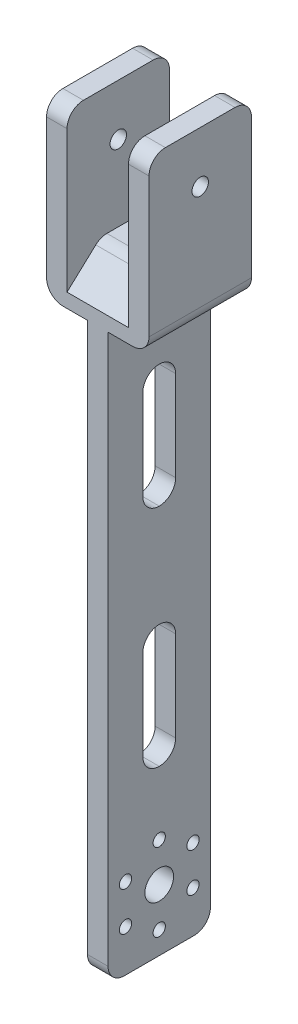
SolidWorks part; units mm, degrees
ref_plane "Ön Düzlem" through (0, 0, 0) normal (0, 0, 1) x (1, 0, 0)
ref_plane "Üst Düzlem" through (0, 0, 0) normal (0, 1, 0) x (1, 0, 0)
ref_plane "Sağ Düzlem" through (0, 0, 0) normal (1, 0, 0) x (0, 0, -1)
sketch "Çizim1" plane through (0, 0, 0) normal (0, 0, 1) x (1, 0, 0)
  line L0 (-2.5, 69) -> (-12.5, 69)
  line L1 (2.5, -69) -> (-2.5, -69)
  line L2 (2.5, -69) -> (2.5, 69)
  line L4 (-2.5, -69) -> (-2.5, 69)
  line L5 (2.5, -69) -> (-2.5, 69) construction
  line L6 (2.5, 69) -> (-2.5, -69) construction
  line L7 (-12.5, 69) -> (-12.5, 111)
  line L8 (-12.5, 111) -> (-7.5, 111)
  line L9 (-7.5, 111) -> (-7.5, 80)
  line L10 (-7.5, 80) -> (7.5, 80)
  line L11 (7.5, 80) -> (7.5, 111)
  line L12 (7.5, 111) -> (12.5, 111)
  line L13 (12.5, 111) -> (12.5, 69)
  line L14 (12.5, 69) -> (2.5, 69)
  point P0 (0, 0)
  dimension "D1" = 138
  dimension "D2" = 5
  dimension "D3" = 10
  dimension "D4" = 42
  dimension "D5" = 5
  dimension "D6" = 31
  dimension "D7" = 15
  dimension "D8" = 42
  dimension "D9" = 5
  dimension "D10" = 138
extrude "Yükseklik-Ekstrüzyon1" add sketch "Çizim1" along normal blind 25
sketch "Çizim2" plane through (-12.5, 0, 0) normal (-1, 0, 0) x (0, 0, 1)
  line L0 (0, 111) -> (0, 69) construction
  line L2 (25, 111) -> (0, 111) construction
  circle A0 centre (12.5, 98.5) radius 2
  dimension "D3" = 4
  dimension "D1" = 12.5
  dimension "D2" = 12.5
extrude "Kes-Ekstrüzyon1" cut sketch "Çizim2" against normal blind 25
sketch "Çizim3" plane through (-2.5, 0, 0) normal (-1, 0, 0) x (0, 0, 1)
  line L0 (25, 69) -> (25, -69) construction
  line L1 (8.5, 56) -> (16.5, 56)
  line L2 (8.5, 56) -> (8.5, 26)
  line L3 (8.5, 26) -> (16.5, 26)
  line L4 (16.5, 56) -> (16.5, 26)
  line L5 (8.5, 1) -> (16.5, 1)
  line L6 (8.5, 1) -> (8.5, -29)
  line L7 (8.5, -29) -> (16.5, -29)
  line L8 (16.5, 1) -> (16.5, -29)
  line L9 (25, -69) -> (0, -69) construction
  line L10 (0, 69) -> (0, -69) construction
  circle A0 centre (12.5, -54) radius 3.5
  dimension "D1" = 7
  dimension "D2" = 12.5
  dimension "D3" = 15
  dimension "D4" = 8.5
  dimension "D5" = 8.5
  dimension "D6" = 25
  dimension "D7" = 40
  dimension "D8" = 30
  dimension "D9" = 30
  dimension "D10" = 8.5
  dimension "D11" = 8.5
extrude "Kes-Ekstrüzyon2" cut sketch "Çizim3" against normal blind 10
sketch "Çizim4" plane through (-2.5, 0, 0) normal (-1, 0, 0) x (0, 0, 1)
  line L0 (25, 69) -> (25, -69) construction
  circle A0 centre (12.5, -44.5) radius 1.5
  dimension "D3" = 3
  dimension "D1" = 12.5
  dimension "D2" = 9.5
extrude "Kes-Ekstrüzyon3" cut sketch "Çizim4" against normal blind 10
pattern_circular "Dairesel Kaplama2" count 6 over 360 about axis through (7.5, -54, 12.5) along (-1, 0, 0) of "Kes-Ekstrüzyon3"
ref_plane "Plane1" through (0, 0, 0) normal (1, 0, 0) x (0, 0, -1)
sketch "Sketch2" plane through (0, 0, 0) normal (1, 0, 0) x (0, 0, -1)
  line L0 (-12.5, 0) -> (-12.5, 84) construction
  line L4 (0, 0) -> (-27.6764, 0) construction
  line L6 (-12.5, 84) -> (-25.5, 72)
  line L8 (-12.5, 84) -> (0.5, 72)
  line L9 (0.5, 72) -> (0.5, 86)
  line L10 (-25.5, 72) -> (-25.5, 86)
  line L11 (0.5, 86) -> (-25.5, 86)
  point P3 (0, 0)
  dimension "D1" = 12.5
  dimension "D2" = 84
  dimension "D3" = 13
  dimension "D4" = 13
  dimension "D5" = 12
  dimension "D6" = 12
  dimension "D7" = 14
  dimension "D8" = 14
extrude "Cut-Extrude8" cut sketch "Sketch2" against normal mid plane 15
fillet "Radyus1" radius 4 18 edges at (-10, 111, 25) (10, 111, 25) (10, 111, 0) (-10, 111, 0) (0, 26, 16.5) (0, 56, 16.5) (0, 26, 8.5) (0, 56, 8.5) (0, -29, 16.5) (0, -29, 8.5) (0, 1, 16.5) (0, 1, 8.5) (0, -69, 25) (0, -69, 0) (0, 80, 16.8333) (0, 80, 8.1667) (12.5, 69, 12.5) (-12.5, 69, 12.5)
